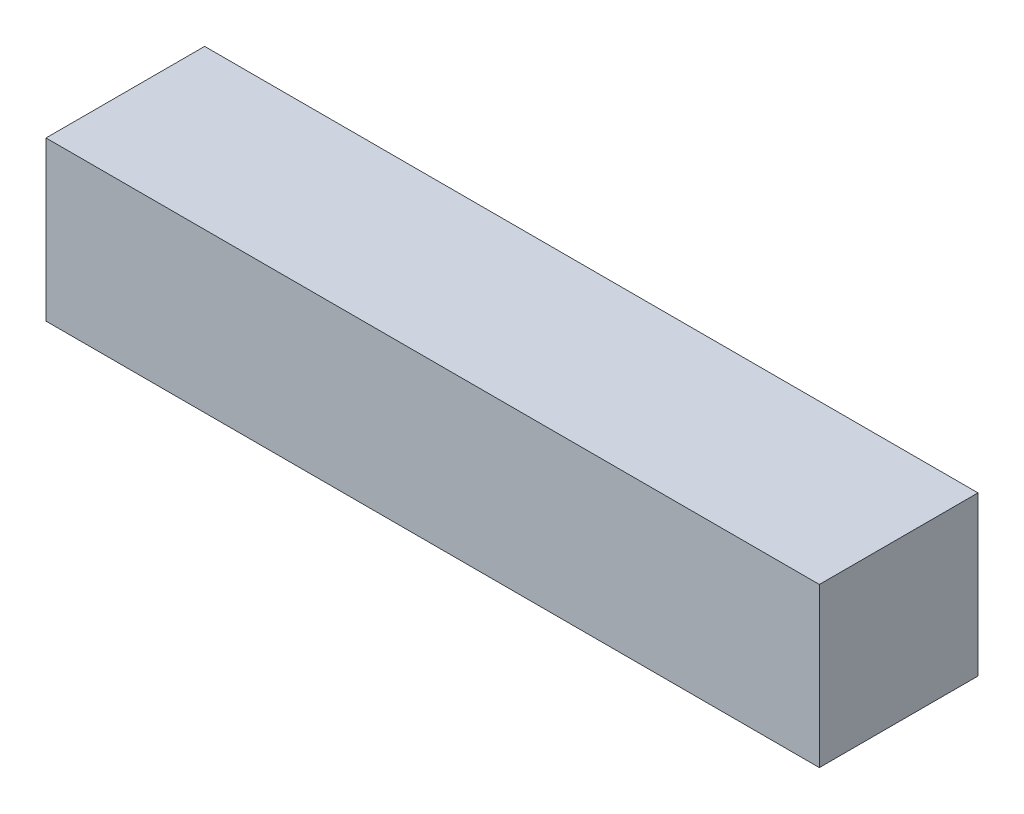
SolidWorks part; units mm, degrees
material "1.0037 (S235JR)"
ref_plane "Front Plane" through (0, 0, 0) normal (0, 0, 1) x (1, 0, 0)
ref_plane "Top Plane" through (0, 0, 0) normal (0, 1, 0) x (1, 0, 0)
ref_plane "Right Plane" through (0, 0, 0) normal (1, 0, 0) x (0, 0, -1)
sketch "Sketch1" plane through (0, 0, 0) normal (0, 0, 1) x (1, 0, 0)
  line L0 (0, 0) -> (0, 309.1855) construction
  line L1 (-585, 0) -> (585, 0)
  line L2 (-585, 0) -> (-585, 240)
  line L3 (-585, 240) -> (585, 240)
  line L4 (585, 0) -> (585, 240)
  dimension "D1" = 1170
  dimension "D2" = 240
extrude "Boss-Extrude1" add sketch "Sketch1" along normal mid plane 240
ref_axis "Axis1" through (0, 290.6767, 0) along (0, -1, 0)
